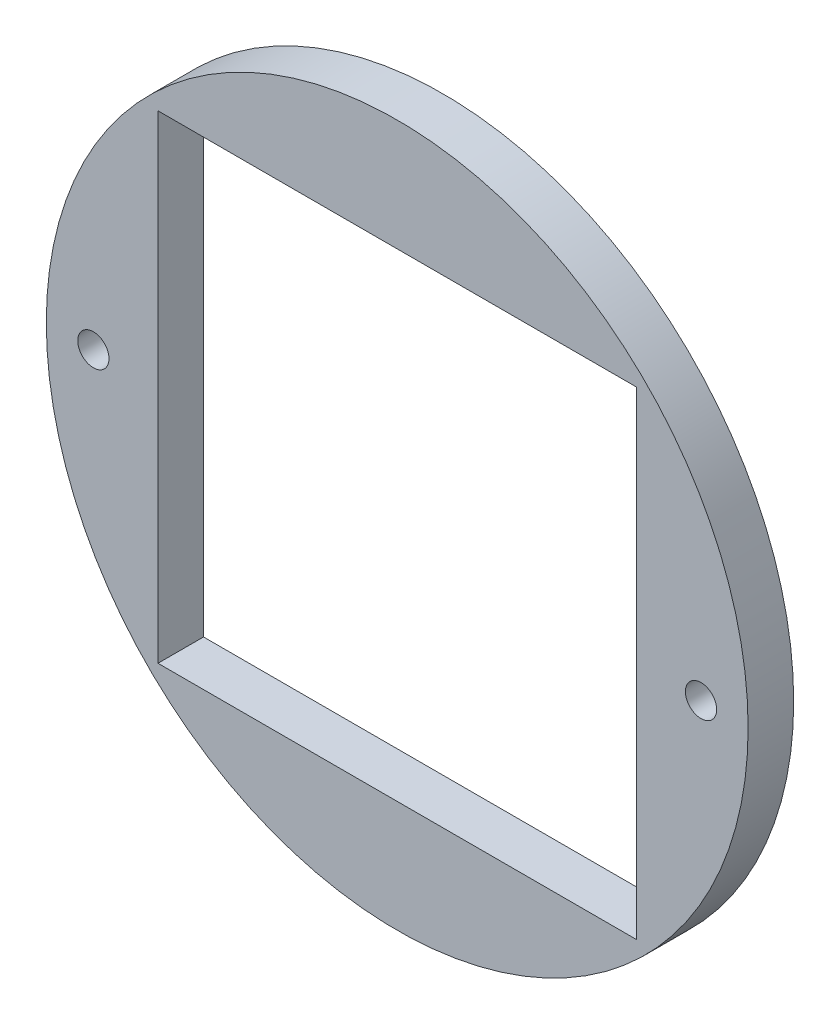
SolidWorks part; units mm, degrees
material "6061 Alloy"
ref_plane "Front Plane" through (0, 0, 0) normal (0, 0, 1) x (1, 0, 0)
ref_plane "Top Plane" through (0, 0, 0) normal (0, 1, 0) x (1, 0, 0)
ref_plane "Right Plane" through (0, 0, 0) normal (1, 0, 0) x (0, 0, -1)
sketch "Sketch1" plane through (0, 0, 0) normal (0, 0, 1) x (1, 0, 0)
  circle A0 centre (0, 0) radius 73.3425
  dimension "D1" = 146.685
extrude "Boss-Extrude1" add sketch "Sketch1" along normal blind 9.525
sketch "Sketch2" plane through (0, 0, 9.525) normal (0, 0, 1) x (1, 0, 0)
  point P0 (-63.5, 0)
  point P1 (63.5, 0)
  point P2 (0, 0)
  dimension "D1" = 63.5
  dimension "D2" = 63.5
hole_wizard "1/4 Clearance Hole1" positions "Sketch2" profile "Sketch3" hole size "1/4" standard "ANSI Inch" end condition through all
sketch "Sketch3" plane through (-63.5, 0, 9.525) normal (1, 0, 0) x (0, -1, 0)
  line L0 (0, 0) -> (0, 9.525)
  line L1 (0, 9.525) -> (3.2639, 9.525)
  line L2 (3.2639, 9.525) -> (3.2639, 0)
  line L5 (3.2639, 0) -> (0, 0)
  line L11 (0, -6.35) -> (0, 107.95) construction
  dimension "Thru Hole Dia." = 6.5278
  dimension "Thru Hole Depth" = 9.525
sketch "Sketch4" plane through (0, 0, 9.525) normal (0, 0, 1) x (1, 0, 0)
  line L1 (-50, -50) -> (50, -50)
  line L2 (-50, -50) -> (-50, 50)
  line L3 (-50, 50) -> (50, 50)
  line L4 (50, -50) -> (50, 50)
  line L5 (-50, -50) -> (50, 50) construction
  line L6 (-50, 50) -> (50, -50) construction
  point P0 (0, 0)
  dimension "D1" = 100
  dimension "D2" = 100
extrude "Cut-Extrude1" cut sketch "Sketch4" against normal through all both and the other way through all
equation "\"outerdiameter\" = 5.775"
equation "\"platethickness\"= 0.375"
equation "\"holespacing\"= 2.5"
equation "\"D1@Sketch1\"=\"outerdiameter\""
equation "\"D1@Boss-Extrude1\"=\"platethickness\""
equation "\"D1@Sketch2\"=\"holespacing\""
equation "\"D2@Sketch2\"=\"holespacing\""
equation "\"cutclearance\"= 100mm"
equation "\"D1@Sketch4\"=\"cutclearance\""
equation "\"D2@Sketch4\"=\"cutclearance\""
